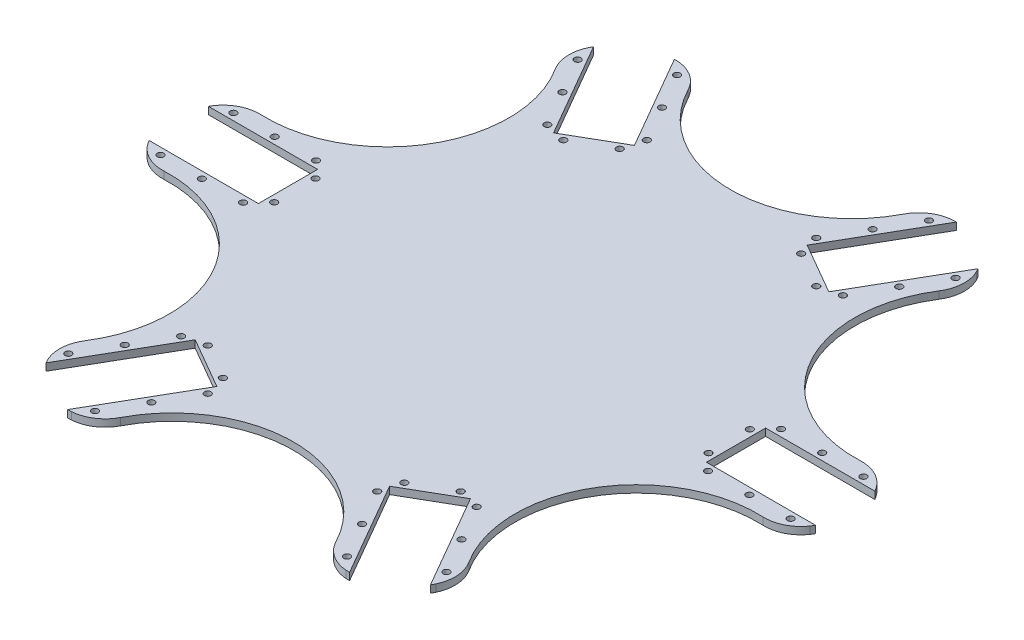
SolidWorks part; units mm, degrees
material "1060-H12"
ref_plane "Front Plane" through (0, 0, 0) normal (0, 0, 1) x (1, 0, 0)
ref_plane "Top Plane" through (0, 0, 0) normal (0, 1, 0) x (1, 0, 0)
ref_plane "Right Plane" through (0, 0, 0) normal (1, 0, 0) x (0, 0, -1)
sketch "Sketch2" plane through (0, 0, 0) normal (0, 1, 0) x (1, 0, 0)
  line L1 (0, 125) -> (-58.0814, 125)
  line L2 (-35.5814, 86.0289) -> (-56.7125, 73.8289)
  line L3 (-79.2125, 112.8) -> (-108.2532, 62.5)
  line L4 (-35.5814, 86.0289) -> (-58.0814, 125)
  line L7 (0, 0) -> (0, 125)
  line L8 (0, 0) -> (-108.2532, 62.5)
  line L12 (-79.2125, 112.8) -> (-56.7125, 73.8289)
  circle A0 centre (-37.3857, 81.754) radius 1.35
  circle A1 centre (-52.1082, 73.254) radius 1.35
  circle A2 centre (-60.8873, 75.4599) radius 1.35
  circle A3 centre (-34.9066, 90.4599) radius 1.35
  circle A4 centre (-51.9066, 119.9048) radius 1.35
  circle A5 centre (-43.4066, 105.1824) radius 1.35
  circle A6 centre (-69.3873, 90.1824) radius 1.35
  circle A7 centre (-77.8873, 104.9048) radius 1.35
  dimension "D3" = 3.5
  dimension "D5" = 2.8
  dimension "D9" = 34
  dimension "D13" = 2.8
  dimension "D14" = 2.8
  dimension "D2" = 3.5
  dimension "D4" = 17
  dimension "D6" = 2.8
  dimension "D12" = 17
  dimension "D15" = 17
  dimension "D16" = 34
extrude "Boss-Extrude1" add sketch "Sketch2" along normal blind 3
pattern_circular "CirPattern1" count 6 over 360 about axis through (0, 3, 0) along (0, -1, 0) of "Boss-Extrude1"
sketch "Sketch4" plane through (0, 3, 0) normal (0, 1, 0) x (1, 0, 0)
  line L0 (58.0814, 125) -> (-58.0814, 125) construction
  line L1 (137.2939, 12.2) -> (79.2125, 112.8) construction
  line L2 (79.2125, -112.8) -> (137.2939, -12.2) construction
  line L3 (-58.0814, -125) -> (58.0814, -125) construction
  line L4 (-137.2939, -12.2) -> (-79.2125, -112.8) construction
  line L5 (-79.2125, 112.8) -> (-137.2939, 12.2) construction
  line L6 (79.2125, -112.8) -> (137.2939, -12.2)
  line L8 (137.2939, 12.2) -> (79.2125, 112.8)
  line L10 (58.0814, 125) -> (-58.0814, 125)
  line L12 (-79.2125, 112.8) -> (-137.2939, 12.2)
  line L14 (-92.2939, -12.2) -> (-137.2939, -12.2) construction
  line L15 (-137.2939, -12.2) -> (-79.2125, -112.8)
  line L17 (-58.0814, -125) -> (58.0814, -125)
  arc A0 (-30.9451, 108.6476) -> (30.9451, 108.6476) centre (0, 125) ccw
  arc A1 (78.619, 81.123) -> (109.5641, 27.5246) centre (108.2532, 62.5) ccw
  arc A2 (109.5641, -27.5246) -> (78.619, -81.123) centre (108.2532, -62.5) ccw
  arc A4 (-78.619, -81.123) -> (-109.5641, -27.5246) centre (-108.2532, -62.5) ccw
  arc A5 (-109.5641, 27.5246) -> (-78.619, 81.123) centre (-108.2532, 62.5) ccw
  arc A6 (58.0814, 125) -> (30.9451, 108.6476) centre (58.0814, 94.3078) ccw
  arc A7 (-30.9451, 108.6476) -> (-58.0814, 125) centre (-58.0814, 94.3078) ccw
  arc A8 (-79.2125, 112.8) -> (-78.619, 81.123) centre (-52.6322, 97.4539) ccw
  arc A9 (-109.5641, 27.5246) -> (-137.2939, 12.2) centre (-110.7137, -3.1461) ccw
  arc A10 (109.5641, -27.5246) -> (137.2939, -12.2) centre (110.7137, 3.1461) ccw
  arc A11 (-58.0814, -125) -> (-30.9451, -108.6476) centre (-58.0814, -94.3078) ccw
  arc A12 (-78.619, -81.123) -> (-79.2125, -112.8) centre (-52.6322, -97.4539) ccw
  arc A13 (-137.2939, -12.2) -> (-109.5641, -27.5246) centre (-110.7137, 3.1461) ccw
  arc A14 (78.619, 81.123) -> (79.2125, 112.8) centre (52.6322, 97.4539) ccw
  arc A16 (79.2125, -112.8) -> (78.619, -81.123) centre (52.6322, -97.4539) ccw
  arc A19 (137.2939, 12.2) -> (109.5641, 27.5246) centre (110.7137, -3.1461) ccw
  arc A20 (30.9451, -108.6476) -> (-30.9451, -108.6476) centre (0, -125) ccw
  arc A21 (30.9451, -108.6476) -> (58.0814, -125) centre (58.0814, -94.3078) ccw
extrude "Cut-Extrude3" cut sketch "Sketch4" against normal blind 5
sketch "Sketch9" plane through (0, 3, 0) normal (0, 1, 0) x (1, 0, 0)
  line L0 (-46.1469, 79.9289) -> (-62.6469, 108.5077) construction
  line L1 (-58.0814, 125) -> (58.0814, 125)
  line L2 (79.2125, 112.8) -> (137.2939, 12.2)
  line L3 (-35.5814, 86.0289) -> (-56.7125, 73.8289) construction
  line L4 (137.2939, -12.2) -> (79.2125, -112.8)
  line L5 (46.1469, 79.9289) -> (62.6469, 108.5077) construction
  line L6 (56.7125, 73.8289) -> (35.5814, 86.0289) construction
  line L7 (58.0814, -125) -> (-58.0814, -125)
  line L8 (-79.2125, -112.8) -> (-137.2939, -12.2)
  line L9 (-137.2939, 12.2) -> (-79.2125, 112.8)
  arc A0 (-44.3583, 116.9275) -> (44.3583, 116.9275) centre (0, 140) ccw
  arc A1 (-44.3583, 116.9275) -> (-58.0814, 125) centre (-57.6658, 110.0058) ccw
  circle A2 centre (-62.6469, 108.5077) radius 25 construction
  circle A3 centre (62.6469, 108.5077) radius 25 construction
  arc A4 (-30.9451, 108.6476) -> (30.9451, 108.6476) centre (0, 125) ccw construction
  arc A5 (58.0814, 125) -> (44.3583, 116.9275) centre (57.6658, 110.0058) ccw
  arc A6 (79.083, 96.8792) -> (79.2125, 112.8) centre (66.4349, 104.9429) ccw
  arc A7 (79.083, 96.8792) -> (123.4413, 20.0483) centre (121.2436, 70) ccw
  arc A8 (137.2939, 12.2) -> (123.4413, 20.0483) centre (124.1007, 5.0628) ccw
  arc A9 (123.4413, -20.0483) -> (137.2939, -12.2) centre (124.1007, -5.0628) ccw
  arc A10 (123.4413, -20.0483) -> (79.083, -96.8792) centre (121.2436, -70) ccw
  arc A11 (79.2125, -112.8) -> (79.083, -96.8792) centre (66.4349, -104.9429) ccw
  arc A12 (44.3583, -116.9275) -> (58.0814, -125) centre (57.6658, -110.0058) ccw
  arc A13 (44.3583, -116.9275) -> (-44.3583, -116.9275) centre (0, -140) ccw
  arc A14 (-58.0814, -125) -> (-44.3583, -116.9275) centre (-57.6658, -110.0058) ccw
  arc A15 (-79.083, -96.8792) -> (-79.2125, -112.8) centre (-66.4349, -104.9429) ccw
  arc A16 (-79.083, -96.8792) -> (-123.4413, -20.0483) centre (-121.2436, -70) ccw
  arc A17 (-137.2939, -12.2) -> (-123.4413, -20.0483) centre (-124.1007, -5.0628) ccw
  arc A18 (-123.4413, 20.0483) -> (-137.2939, 12.2) centre (-124.1007, 5.0628) ccw
  arc A19 (-123.4413, 20.0483) -> (-79.083, 96.8792) centre (-121.2436, 70) ccw
  arc A20 (-79.2125, 112.8) -> (-79.083, 96.8792) centre (-66.4349, 104.9429) ccw
  point P8 (0, 90)
  point P61 (0, 0)
  dimension "D1" = 6
extrude "Cut-Extrude9" cut sketch "Sketch9" against normal blind 10 contours A5 L1 A1 A0 | A20 L9 A18 A19 | A17 L8 A15 A16 | A8 L2 A6 A7 | A11 L4 A9 A10 | A14 L7 A12 A13 region at (0, 3, -110.6371) region at (95.8145, 3, -55.3185) region at (95.8145, 3, 55.3185) region at (0, 3, 110.6371) region at (-95.8145, 3, 55.3185) region at (-95.8145, 3, -55.3185)
